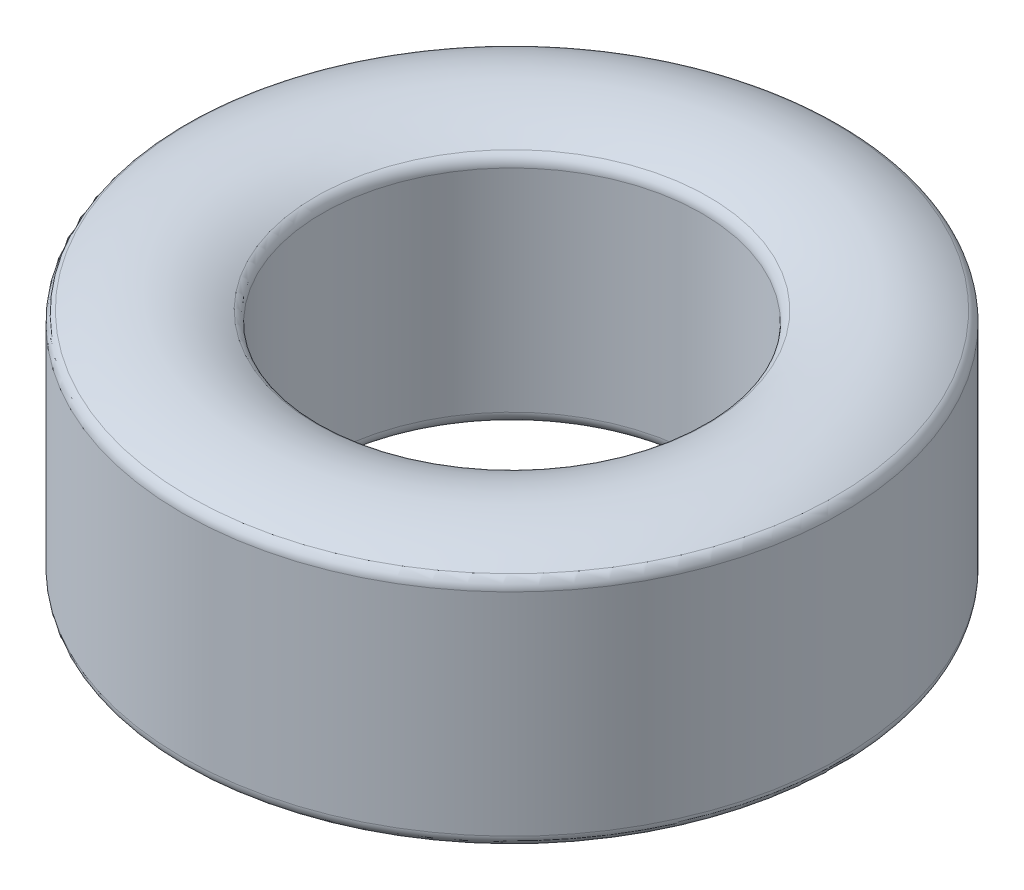
SolidWorks part; units mm, degrees
ref_plane "Front Plane" through (0, 0, 0) normal (0, 0, 1) x (1, 0, 0)
ref_plane "Top Plane" through (0, 0, 0) normal (0, 1, 0) x (1, 0, 0)
ref_plane "Right Plane" through (0, 0, 0) normal (1, 0, 0) x (0, 0, -1)
sketch "Sketch1" plane through (0, 0, 0) normal (1, 0, 0) x (0, 0, -1)
  line L0 (0, 59.1222) -> (0, -46.6086) construction
  line L1 (-7.5, 4.1779) -> (-7.5, -4.1779)
  line L2 (-13.02, 4.1779) -> (-13.02, -4.1779)
  line L3 (-20.8257, 5.25) -> (-1.7185, 5.25) construction
  line L4 (-39.1478, 0) -> (37.4253, 0) construction
  arc A0 (-12.7579, 4.6177) -> (-7.7621, 4.6177) centre (-10.26, 0) cw
  arc A1 (-12.7579, -4.6177) -> (-7.7621, -4.6177) centre (-10.26, 0) ccw
  arc A2 (-7.5, -4.1779) -> (-7.7621, -4.6177) centre (-8, -4.1779) cw
  arc A3 (-13.02, -4.1779) -> (-12.7579, -4.6177) centre (-12.52, -4.1779) ccw
  arc A4 (-7.7621, 4.6177) -> (-7.5, 4.1779) centre (-8, 4.1779) cw
  arc A5 (-13.02, 4.1779) -> (-12.7579, 4.6177) centre (-12.52, 4.1779) cw
  point P6 (-13.02, 11.5427)
  point P10 (-7.5, 0)
  point P14 (0, 0)
  point P15 (0, 0)
  point P16 (37.4253, 0)
  point P19 (-7.5, -4.466)
  point P22 (-13.02, -4.466)
  point P25 (-7.5, 4.466)
  point P28 (-13.02, 4.466)
  dimension "D1" = 5.25
  dimension "D4" = 0.5
  dimension "D2" = 5.52
  dimension "D3" = 15
revolve "Revolve1" add sketch "Sketch1" angle 360 about L0
